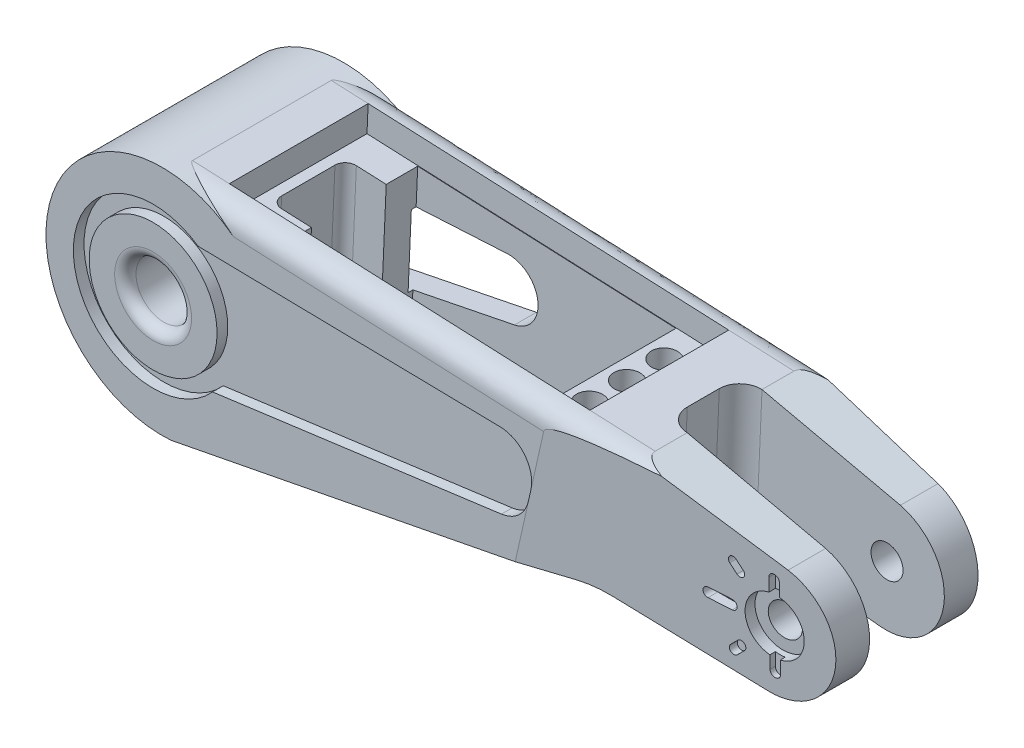
SolidWorks part; units mm, degrees
ref_plane "前视基准面" through (0, 0, 0) normal (0, 0, 1) x (1, 0, 0)
ref_plane "上视基准面" through (0, 0, 0) normal (0, 1, 0) x (1, 0, 0)
ref_plane "右视基准面" through (0, 0, 0) normal (1, 0, 0) x (0, 0, -1)
sketch "草图1" plane through (0, 0, 0) normal (0, 0, 1) x (1, 0, 0)
  line L2 (-19.4532, -0.6445) -> (19.7335, 6.9761)
  line L4 (-19.4532, 21.0492) -> (23.8765, 19.1407)
  line L9 (23.8765, 19.1407) -> (36.8454, 16.2397)
  line L10 (19.7335, 6.9761) -> (35.0831, 5.4643)
  circle A5 centre (-21.1408, 10.2023) radius 2.6 construction
  circle A6 centre (-21.1408, 10.2023) radius 2.6
  circle A7 centre (35.5914, 11.0768) radius 1.5
  arc A13 (35.0831, 5.4643) -> (36.8454, 16.2397) centre (35.4798, 10.9312) ccw
  arc A15 (-19.4532, 21.0492) -> (-19.4532, -0.6445) centre (-20.297, 10.2023) ccw
  dimension "D2" = 3
  dimension "D6" = 5.2
extrude "凸台-拉伸1" add sketch "草图1" along normal blind 17
sketch "草图5" plane through (0.8877, 20.1532, 0) normal (0.044, 0.999, 0) x (0.999, -0.044, 0)
  line L0 (-2.1258, -8.5) -> (9.9742, -8.5) construction
  line L1 (-12.1, -2.05) -> (12.1, -2.05)
  line L2 (-12.1, -2.05) -> (-12.1, -14.95) construction
  line L3 (-12.1, -14.95) -> (12.1, -14.95)
  line L4 (12.1, -2.05) -> (12.1, -14.95)
  line L5 (-12.1, -2.05) -> (12.1, -14.95) construction
  line L6 (-12.1, -14.95) -> (12.1, -2.05) construction
  line L7 (-14, -5) -> (14, -5) construction
  line L8 (-14, -5) -> (-14, -12) construction
  line L9 (-14, -12) -> (14, -12) construction
  line L10 (14, -5) -> (14, -12) construction
  line L11 (-14, -5) -> (14, -12) construction
  line L12 (-14, -12) -> (14, -5) construction
  line L13 (-12.1, -2.05) -> (-12.1, -5)
  line L14 (21.0181, -5) -> (64.762, -5)
  line L15 (21.0181, -5) -> (21.0181, -12)
  line L16 (21.0181, -12) -> (64.762, -12)
  line L17 (64.762, -5) -> (64.762, -12)
  line L18 (21.0181, -5) -> (64.762, -12) construction
  line L19 (21.0181, -12) -> (64.762, -5) construction
  line L20 (-15.9, -5) -> (-12.1, -5)
  line L21 (-15.9, -5) -> (-15.9, -12)
  line L22 (-15.9, -12) -> (-12.1, -12)
  line L23 (-12.1, -5) -> (-12.1, -12) construction
  line L24 (-15.9, -5) -> (-12.1, -12) construction
  line L25 (-15.9, -12) -> (-12.1, -5) construction
  line L26 (-12.1, -12) -> (-12.1, -14.95)
  line L27 (-25.9783, -8.5) -> (-22.2059, -8.5) construction
  circle A0 centre (-14, -5) radius 1.25 construction
  circle A1 centre (-14, -12) radius 1.25 construction
  circle A2 centre (14, -5) radius 1.25
  circle A3 centre (14, -12) radius 1.25
  circle A4 centre (-14, -8.5) radius 1.25 construction
  circle A5 centre (14, -8.5) radius 1.25
  point P0 (0, -8.5)
  point P5 (0, -8.5)
  point P23 (42.89, -8.5)
  dimension "D5" = 2.5
  dimension "D6" = 2.5
  dimension "D7" = 2.5
  dimension "D8" = 2.5
  dimension "D9" = 7
  dimension "D1" = 24.2
  dimension "D2" = 12.9
  dimension "D3" = 28
  dimension "D4" = 7
  dimension "D10" = 0
extrude "切除-拉伸2" cut sketch "草图5" against normal through all both and the other way through all
sketch "草图7" plane through (12.0883, -0.5324, 0) normal (-0.999, 0.044, 0) x (0, 0, 1)
  line L0 (2.05, 6.0797) -> (2.05, 20.1728) construction
  line L1 (2.05, 15.1728) -> (14.95, 15.1728)
  line L2 (2.05, 15.1728) -> (2.05, 3.1935)
  line L3 (2.05, 3.1935) -> (14.95, 3.1935)
  line L4 (14.95, 15.1728) -> (14.95, 3.1935)
  line L5 (14.95, 6.0797) -> (14.95, 20.1728) construction
  line L6 (2.05, 20.1728) -> (14.95, 20.1728) construction
  dimension "D1" = 5
extrude "切除-拉伸3" cut sketch "草图7" against normal blind 4
fillet "圆角2" radius 2 2 edges at (2.2116, 20.0949, 0) (2.2116, 20.0949, 17) conic rho 0.5
fillet "圆角3" radius 3 rebuild error yes
sketch "草图8" plane through (5.2154, 23.315, 0) normal (0.2183, 0.9759, 0) x (0.9759, -0.2183, 0)
  line L0 (11.1868, 0) -> (41.8849, -2.1466)
  line L1 (-17.391, 0) -> (30.5415, 0) construction
  line L2 (41.8849, -2.1466) -> (37.5658, 8.2117)
  line L3 (37.5658, 8.2117) -> (11.1868, 0)
  line L4 (11.2348, -17) -> (38.9022, -15.0653)
  line L5 (30.5415, -17) -> (-17.391, -17) construction
  line L6 (38.9022, -15.0653) -> (33.4878, -36.0011)
  line L7 (33.4878, -36.0011) -> (11.2348, -17)
  line L8 (32.4117, -17) -> (30.5415, -17) construction
  line L9 (36.3426, 0) -> (32.0305, 0) construction
  dimension "D1" = 4
  dimension "D2" = 4
extrude "切除-拉伸4" cut sketch "草图8" against normal through all both and the other way through all
sketch "草图9" plane through (0.8877, 20.1532, 0) normal (0.044, 0.999, 0) x (0.999, -0.044, 0)
  line L0 (23.0111, -2) -> (-20.3606, -2) construction
  line L1 (-16.9054, -2) -> (16.8949, -2)
  line L2 (-16.9054, -2) -> (-16.9054, -15)
  line L3 (-16.9054, -15) -> (16.8949, -15)
  line L4 (16.8949, -2) -> (16.8949, -15)
  line L5 (-20.3606, -15) -> (23.0111, -15) construction
extrude "切除-拉伸5" cut sketch "草图9" against normal blind 2.5
sketch "草图10" plane through (0, 0, 0) normal (0, 0, -1) x (-1, 0, 0)
  circle A0 centre (21.1408, 10.2023) radius 3.9889
  circle A1 centre (21.1408, 10.2023) radius 1.1
  dimension "D1" = 2.2
extrude "凸台-拉伸2" add sketch "草图10" against normal blind 9
sketch "草图11" plane through (0, 0, 0) normal (0, 0, -1) x (-1, 0, 0)
  line L4 (2.2472, 9.8443) -> (20.4137, 6.1927)
  line L5 (2.9414, 15.2862) -> (21.1408, 14.2773)
  circle A0 centre (21.1408, 10.2023) radius 4.075 construction
  circle A1 centre (2.7892, 12.5404) radius 2.75 construction
  arc A5 (2.9414, 15.2862) -> (2.2472, 9.8443) centre (2.7892, 12.5404) ccw
  arc A6 (21.1408, 14.2773) -> (20.4137, 6.1927) centre (21.1408, 10.2023) cw
  dimension "D1" = 8.15
  dimension "D3" = 5.5
  dimension "D2" = 18.5
extrude "切除-拉伸6" cut sketch "草图11" against normal blind 2.5
fillet "圆角5" radius 2 2 edges at (21.6121, 13.0232, 5) (21.6121, 13.0232, 12)
sketch "草图13" plane through (0, 0, 2.5) normal (0, 0, -1) x (-1, 0, 0)
  circle A0 centre (21.1408, 10.2023) radius 3.625
  dimension "D1" = 7.25
extrude "切除-拉伸7" cut sketch "草图13" against normal blind 1
fillet "圆角7" radius 1 1 edges at (-18.5408, 10.2023, 17)
fillet "圆角8" radius 11 1 edges at (19.7335, 6.9761, 8.5017)
sketch "草图16" plane through (0, 0, 17) normal (0, 0, 1) x (1, 0, 0)
  line L0 (15.0453, 15.7934) -> (-16.9221, 16.3666)
  line L1 (13.5523, 9.1193) -> (-15.5729, 5.223)
  line L2 (12.77, 5.6219) -> (15.4294, 17.5108) construction
  line L3 (15.0453, 15.7934) -> (13.5523, 9.1193)
  circle A0 centre (-21.1408, 10.2023) radius 5.9907
  circle A1 centre (-21.1408, 10.2023) radius 7.4697 construction
  arc A2 (-16.9221, 16.3666) -> (-15.5729, 5.223) centre (-21.1408, 10.2023) ccw
extrude "切除-拉伸8" cut sketch "草图16" against normal blind 1
fillet "圆角9" radius 3 2 edges at (13.5523, 9.1193, 16.5) (15.0453, 15.7934, 16.5)
sketch "草图17" plane through (1.2078, -0.2702, 17.6991) normal (0.0681, -0.0152, 0.9976) x (0.9977, 0.001, -0.0681)
  circle A0 centre (34.4635, 11.3125) radius 2.6
  dimension "D1" = 5.2
extrude "切除-拉伸9" cut sketch "草图17" against normal blind 1
sketch "草图18" plane through (0.0531, -0.0119, -0.7785) normal (0.0681, -0.0152, -0.9976) x (-0.9977, -0.001, -0.0681)
  circle A0 centre (-35.6209, 11.0529) radius 2.6
  dimension "D1" = 5.2
extrude "切除-拉伸10" cut sketch "草图18" against normal blind 1
fillet "圆角10" radius 1 2 edges at (-15.5102, 9.1996, 5) (-15.5102, 9.1996, 12)
sketch "草图19" plane through (0, 0, 16) normal (0, 0, 1) x (1, 0, 0)
  line L0 (-21.1408, 10.2023) -> (35.5981, 10.2023) construction
  line L1 (35.5981, 10.2023) -> (35.5981, 22.1291) construction
  line L2 (31.8727, 11.094) -> (29.7419, 11.094) construction
  line L3 (31.8727, 10.6598) -> (29.7419, 10.6598)
  line L4 (31.8727, 11.5282) -> (29.7419, 11.5282)
  line L5 (35.5981, 14.8624) -> (35.5981, 7.3257) construction
  line L6 (36.0598, 14.8624) -> (36.0598, 7.3257)
  line L7 (35.1364, 14.8624) -> (35.1364, 7.3257)
  line L8 (35.5981, 11.094) -> (31.9347, 14.7574) construction
  line L9 (35.5915, 11.0766) -> (32.6922, 8.1772) construction
  line L10 (32.6148, 8.0998) -> (31.9812, 7.4662) construction
  line L11 (32.9054, 7.8092) -> (32.2718, 7.1756)
  line L12 (32.3241, 8.3904) -> (31.6905, 7.7568)
  line L13 (32.6148, 14.0774) -> (31.9873, 14.7048) construction
  line L14 (32.3348, 13.7974) -> (31.7073, 14.4249)
  line L15 (32.8947, 14.3573) -> (32.2672, 14.9848)
  arc A0 (31.8727, 10.6598) -> (31.8727, 11.5282) centre (31.8727, 11.094) ccw
  arc A1 (29.7419, 11.5282) -> (29.7419, 10.6598) centre (29.7419, 11.094) ccw
  arc A2 (36.0598, 14.8624) -> (35.1364, 14.8624) centre (35.5981, 14.8624) ccw
  arc A3 (35.1364, 7.3257) -> (36.0598, 7.3257) centre (35.5981, 7.3257) ccw
  arc A4 (32.9054, 7.8092) -> (32.3241, 8.3904) centre (32.6148, 8.0998) ccw
  arc A5 (31.6905, 7.7568) -> (32.2718, 7.1756) centre (31.9812, 7.4662) ccw
  arc A6 (32.3348, 13.7974) -> (32.8947, 14.3573) centre (32.6148, 14.0774) ccw
  arc A7 (32.2672, 14.9848) -> (31.7073, 14.4249) centre (31.9873, 14.7048) ccw
  point P3 (30.8073, 11.094)
  point P14 (35.5981, 11.094)
  point P23 (31.9812, 7.4662)
  point P26 (32.298, 7.783)
  point P31 (32.301, 14.3911)
  point P38 (0, 0)
  point P39 (0, 0)
  point P40 (32.1894, 14.5028)
  point P41 (31.9812, 14.7048)
  dimension "D1" = 90
  dimension "D2" = 45
  dimension "D3" = 45
extrude "切除-拉伸11" cut sketch "草图19" against normal blind 1
